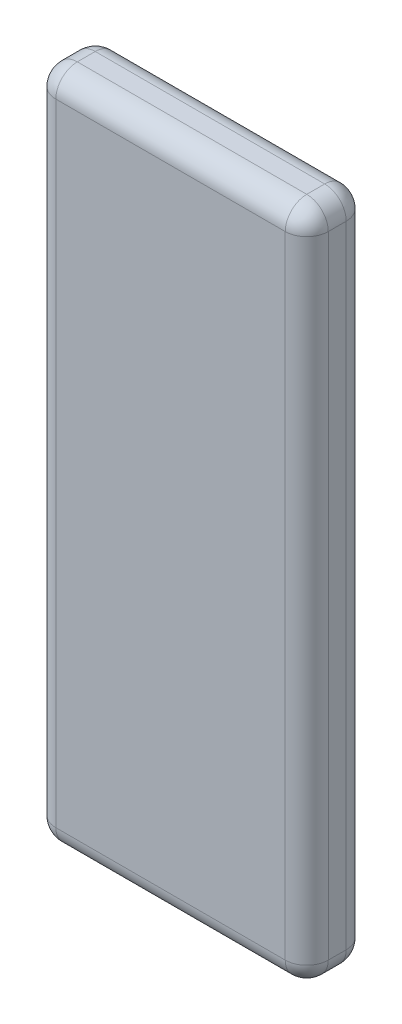
SolidWorks part; units mm, degrees
ref_plane "Front Plane" through (0, 0, 0) normal (0, 0, 1) x (1, 0, 0)
ref_plane "Top Plane" through (0, 0, 0) normal (0, 1, 0) x (1, 0, 0)
ref_plane "Right Plane" through (0, 0, 0) normal (1, 0, 0) x (0, 0, -1)
sketch "Sketch1" plane through (0, 0, 0) normal (0, 1, 0) x (1, 0, 0)
  line L0 (-380, -85) -> (380, -85)
  line L1 (-380, -85) -> (-380, 85)
  line L2 (-380, 85) -> (380, 85)
  line L3 (380, 85) -> (380, -85)
  point P7 (-756.2327, 308.9561)
  dimension "D1" = 760
  dimension "D2" = 170
  dimension "D3" = 380
  dimension "D4" = 85
extrude "Boss-Extrude1" add sketch "Sketch1" along normal blind 940 and the other way blind 940
fillet "Fillet1" radius 60 12 edges at (380, 940, 0) (0, 940, 85) (-380, 940, 0) (0, 940, -85) (380, 0, -85) (380, 0, 85) (380, -940, 0) (0, -940, -85) (0, -940, 85) (-380, -940, 0) (-380, 0, 85) (-380, 0, -85)
